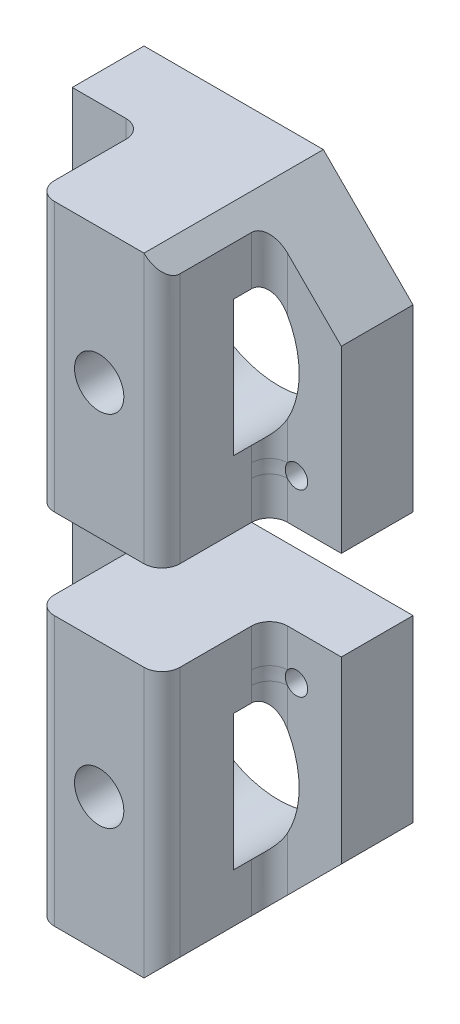
SolidWorks part; units mm, degrees
ref_plane "Front Plane" through (0, 0, 0) normal (0, 0, 1) x (1, 0, 0)
ref_plane "Top Plane" through (0, 0, 0) normal (0, 1, 0) x (1, 0, 0)
ref_plane "Right Plane" through (0, 0, 0) normal (1, 0, 0) x (0, 0, -1)
sketch "Sketch1" plane through (0, 0, 0) normal (0, 0, 1) x (1, 0, 0)
  line L0 (-15, -15) -> (5, -15)
  line L1 (5, -15) -> (15, -5)
  line L2 (-15, -15) -> (-15, 15)
  line L3 (-15, 15) -> (15, 15)
  line L4 (15, -5) -> (15, 15)
  line L5 (-15, -15) -> (15, 15) construction
  line L6 (-15, 15) -> (15, -15) construction
  circle A0 centre (-10, 10) radius 1.25
  circle A1 centre (10, 10) radius 1.25
  circle A2 centre (-10, -10) radius 1.25
  point P0 (0, 0)
  point P11 (0, 0)
  point P14 (0, 0)
  dimension "D3" = 2.5
  dimension "D6" = 20
  dimension "D1" = 30
  dimension "D2" = 30
  dimension "D4" = 20
  dimension "D5" = 135
extrude "Main" add sketch "Sketch1" along normal blind 20
sketch "Sketch2" plane through (0, 0, 0) normal (0, 0, 1) x (1, 0, 0)
  line L0 (-15, -15) -> (15, 15) construction
  line L1 (-15, 15) -> (15, -15) construction
  line L2 (15, -5) -> (15, 15) construction
  line L3 (15, 15) -> (-15, 15) construction
  circle A0 centre (0, 0) radius 10.3
  dimension "D1" = 20.6
extrude "CentralHole" cut sketch "Sketch2" along normal blind 12
sketch "Sketch5" plane through (0, 0, 20) normal (0, 0, 1) x (1, 0, 0)
  line L0 (15, 15) -> (-15, 15) construction
  line L1 (15, -15) -> (7, -15)
  line L2 (15, -15) -> (15, 15)
  line L3 (15, 15) -> (7, 15)
  line L4 (7, -15) -> (7, 15)
  line L5 (-15, -15) -> (5, -15) construction
  line L6 (-15, -15) -> (-7, -15)
  line L7 (-15, -15) -> (-15, 15)
  line L8 (-15, 15) -> (-7, 15)
  line L9 (-7, -15) -> (-7, 15)
  line L10 (15, -5) -> (15, 15) construction
  circle A0 centre (0, 0) radius 2.75
  dimension "D3" = 5.5
  dimension "D1" = 8
  dimension "D2" = 8
extrude "Cut-Extrude3" cut sketch "Sketch5" against normal blind 12
fillet "Fillet1" radius 2 6 edges at (-7, 0, 20) (7, 1, 20) (-7, -11.2779, 8) (-7, 11.2779, 8) (7, 11.2779, 8) (7, -10.2779, 8)
ref_plane "Plane1" through (0, 20, 0) normal (0, 1, 0) x (1, 0, 0)
mirror "Mirror1" about plane through (0, 20, 0) normal (0, 1, 0) of bodies 104
